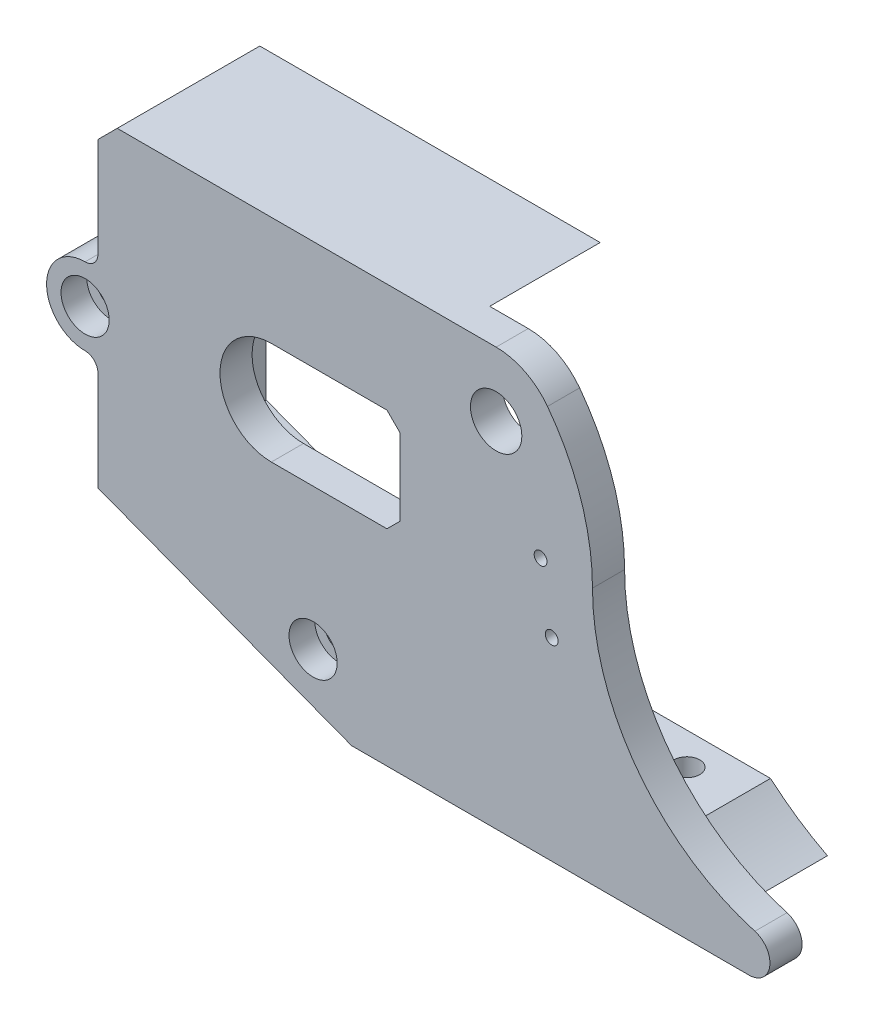
SolidWorks part; units mm, degrees
ref_plane "Front Plane" through (0, 0, 0) normal (0, 0, 1) x (1, 0, 0)
ref_plane "Top Plane" through (0, 0, 0) normal (0, 1, 0) x (1, 0, 0)
ref_plane "Right Plane" through (0, 0, 0) normal (1, 0, 0) x (0, 0, -1)
sketch "Sketch1" plane through (0, 0, 0) normal (0, 0, 1) x (1, 0, 0)
  line L0 (0, -40) -> (-72.5, -40) construction
  line L2 (-112, 25) -> (-112, -25)
  line L3 (-72.5, -40) -> (-20.6155, -40)
  line L4 (-102, 21) -> (-60, 21) construction
  line L5 (-102, 21) -> (-102, -21) construction
  line L6 (-102, -21) -> (-60, -21) construction
  line L7 (-60, 21) -> (-60, -21) construction
  line L8 (-102, 21) -> (-60, -21) construction
  line L9 (-102, -21) -> (-60, 21) construction
  line L10 (-29.4788, -34) -> (-77.0327, -34)
  line L11 (-108, -22.2403) -> (-108, 21)
  line L12 (-108, 21) -> (-60, 21)
  line L13 (-72.5, -40) -> (-112, -25)
  line L14 (-77.0327, -34) -> (-108, -22.2403)
  line L15 (-112, 25) -> (-56, 25)
  arc A0 (-22.016, 33.3961) -> (0, -40) centre (0, 0) cw construction
  arc A1 (-22.016, 33.3961) -> (-60, 21) centre (-63.6326, 96.5245) cw construction
  circle A4 centre (0, 0) radius 40 construction
  arc A6 (-20.6155, -40) -> (-29.4788, -34) centre (0, 0) cw
  circle A10 centre (-50, 15) radius 11 construction
  arc A11 (-60, 21) -> (-56, 25) centre (-50, 15) cw
  point P10 (-81, 0)
  point P25 (-112, 0)
  dimension "D1" = 40
  dimension "D3" = 52
  dimension "D8" = 45
  dimension "D12" = 4
  dimension "D13" = 22
  dimension "D2" = 72.5
  dimension "D4" = 50
  dimension "D5" = 42
  dimension "D6" = 42
  dimension "D7" = 81
  dimension "D9" = 6
  dimension "D10" = 4
  dimension "D11" = 4
  dimension "D14" = 50
  dimension "D15" = 15
extrude "Boss-Extrude1" add sketch "Sketch1" along normal blind 17.2
chamfer "Chamfer3" distance 3 angle 45 1 edges at (-112, 25, 8.6)
chamfer "Chamfer2" distance 2 angle 45 1 edges at (-108, 21, 8.6)
sketch "Sketch2" plane through (0, 0, 17.2) normal (0, 0, 1) x (1, 0, 0)
  line L0 (-85, 8) -> (-65, 8)
  line L1 (-72.5, -40) -> (-20.6155, -40)
  line L4 (-20.6155, -40) -> (-10.6155, -40)
  line L8 (-65, -8) -> (-85, -8)
  line L10 (-56, 25) -> (-109, 25)
  line L11 (-50, 25) -> (-109, 25)
  line L12 (-112, 22) -> (-112, -25)
  line L14 (-72.5, -40) -> (-20.6155, -40)
  line L15 (-29.4788, -34) -> (-77.0327, -34)
  line L16 (-112, -25) -> (-72.5, -40)
  line L17 (-108, -22.2403) -> (-108, 19)
  line L18 (-108, 19) -> (-106, 21)
  line L19 (-106, 21) -> (-60, 21)
  line L22 (-112, 22) -> (-112, -25)
  line L24 (-72.5, -40) -> (0, -40) construction
  line L33 (-112, -25) -> (-72.5, -40)
  line L34 (-77.0327, -34) -> (-108, -22.2403)
  line L35 (-109, 25) -> (-112, 22)
  line L36 (-109, 25) -> (-112, 22)
  line L37 (-65, 8) -> (-65, -8)
  circle A0 centre (-50, 15) radius 4
  arc A1 (-56, 25) -> (-60, 21) centre (-50, 15) ccw construction
  arc A2 (0, -40) -> (-23.5728, 32.316) centre (0, 0) ccw construction
  arc A6 (-29.4788, -34) -> (-20.6155, -40) centre (0, 0) ccw
  arc A8 (-56, 25) -> (-60, 21) centre (-50, 15) ccw
  arc A9 (-85, 8) -> (-85, -8) centre (-85, 0) ccw
  circle A16 centre (-78.5, -30) radius 2.1
  arc A23 (-35, 0) -> (-9.7132, -33.6252) centre (0, 0) ccw
  arc A25 (-35, 0) -> (-42, 21) centre (-70, 0) ccw
  arc A26 (-42, 21) -> (-50, 25) centre (-50, 15) ccw
  arc A28 (-10.6155, -40) -> (-9.7132, -33.6252) centre (-10.6155, -36.7487) ccw
  dimension "D2" = 8
  dimension "D3" = 40
  dimension "D4" = 35
  dimension "D5" = 85
  dimension "D7" = 4.2
  dimension "D8" = 8
  dimension "D6" = 10
  dimension "D9" = 30
  dimension "D10" = 78.5
  dimension "D11" = 20
  dimension "D1" = 0
extrude "Boss-Extrude2" add sketch "Sketch2" along normal blind 5
sketch "Sketch3" plane through (0, 0, 22.2) normal (0, 0, 1) x (1, 0, 0)
  line L0 (-41.3433, -9.8481) -> (-43.0797, 0) construction
  line L1 (0, 0) -> (-46.198, 153.1853) construction
  line L2 (0, 0) -> (0, -8.4365) construction
  circle A0 centre (-43.0797, 0) radius 1
  circle A1 centre (-41.3433, -9.8481) radius 1
  arc A2 (-28.2716, -10.0358) -> (29.1062, 7.2683) centre (0, 0) ccw construction
  arc A3 (-28.2716, -10.0358) -> (-66.0532, 150.7833) centre (678.518, 240.8597) cw construction
  arc A4 (29.1062, 7.2683) -> (-28.3254, 162.1614) centre (-698.5491, -174.4395) ccw construction
  arc A5 (-66.0532, 150.7833) -> (-28.3254, 162.1614) centre (-46.198, 153.1853) cw construction
  dimension "D2" = 2
  dimension "D3" = 2
  dimension "D4" = 30
  dimension "D5" = 20
  dimension "D7" = 750
  dimension "D8" = 750
  dimension "D1" = 10
  dimension "D6" = 160
  dimension "D9" = 10
  dimension "D10" = 42.5
extrude "Cut-Extrude1" cut sketch "Sketch3" against normal up to surface (5 mm away) up to face at (-77, 0, 17.2)
ref_axis "Axis1" through (0, 0, 40.7637) along (0, 0, -1)
sketch "Sketch10" plane through (0, 0, 17.2) normal (0, 0, -1) x (-1, 0, 0)
  line L0 (83.5, -30) -> (83.5, -34)
  line L1 (73.5, -30) -> (73.5, -34)
  line L2 (29.4788, -34) -> (77.0327, -34) construction
  line L4 (73.5, -34) -> (83.5, -34)
  arc A0 (73.5, -30) -> (83.5, -30) centre (78.5, -30) cw
  circle A3 centre (78.5, -30) radius 2.1
  circle A4 centre (78.5, -30) radius 2.1 construction
  dimension "D1" = 10
extrude "Boss-Extrude8" add sketch "Sketch10" along normal up to surface (17.2 mm away) up to face at (-80.921, -5.1882, 0)
sketch "Sketch11" plane through (0, 0, 22.2) normal (0, 0, 1) x (1, 0, 0)
  circle A0 centre (-78.5, -30) radius 3.75
  dimension "D1" = 7.5
extrude "Cut-Extrude2" cut sketch "Sketch11" against normal blind 4
sketch "Sketch12" plane through (0, 0, 22.2) normal (0, 0, 1) x (1, 0, 0)
  line L0 (-114, 4.5) -> (-112, 4.5)
  line L2 (-112, 4.5) -> (-112, -7.5)
  line L3 (-112, -7.5) -> (-114, -7.5)
  line L6 (-112, 22) -> (-112, -25) construction
  arc A0 (-114, 4.5) -> (-114, -7.5) centre (-114, -1.5) ccw
  point P9 (-112, -1.5)
  point P15 (-112, -1.5)
  dimension "D1" = 6
  dimension "D2" = 2
extrude "Boss-Extrude9" add sketch "Sketch12" against normal up to surface (22.2 mm away) up to face at (-80.5346, -9.9202, 0)
fillet "Fillet3" radius 2 2 edges at (-112, -7.5, 11.1) (-112, 4.5, 11.1)
sketch "Sketch13" plane through (0, 0, 22.2) normal (0, 0, 1) x (1, 0, 0)
  circle A0 centre (-114, -1.5) radius 2
  dimension "D1" = 4
extrude "Cut-Extrude3" cut sketch "Sketch13" against normal up to surface (22.2 mm away) up to face at (-87.6416, -8.1475, 0)
sketch "Sketch14" plane through (0, 0, 22.2) normal (0, 0, 1) x (1, 0, 0)
  circle A0 centre (-114, -1.5) radius 3.75
  dimension "D1" = 7.5
extrude "Cut-Extrude4" cut sketch "Sketch14" against normal blind 4
sketch "Sketch15" plane through (0, -40, 0) normal (0, -1, 0) x (1, 0, 0)
  line L0 (-72.5, 0) -> (-20.6155, 0) construction
  circle A0 centre (-37.5, 5) radius 2
  dimension "D1" = 4
  dimension "D2" = 5
  dimension "D3" = 37.5
extrude "Cut-Extrude5" cut sketch "Sketch15" against normal up to surface (6 mm away) up to face at (-51.4894, -34, 8.6)
fillet "Fillet4" radius 2 2 edges at (-73.5, -34, 8.6) (-83.5, -31.5441, 8.6)
chamfer "Chamfer4" distance 2 angle 45 2 edges at (-65, 8, 19.7) (-65, -8, 19.7)
